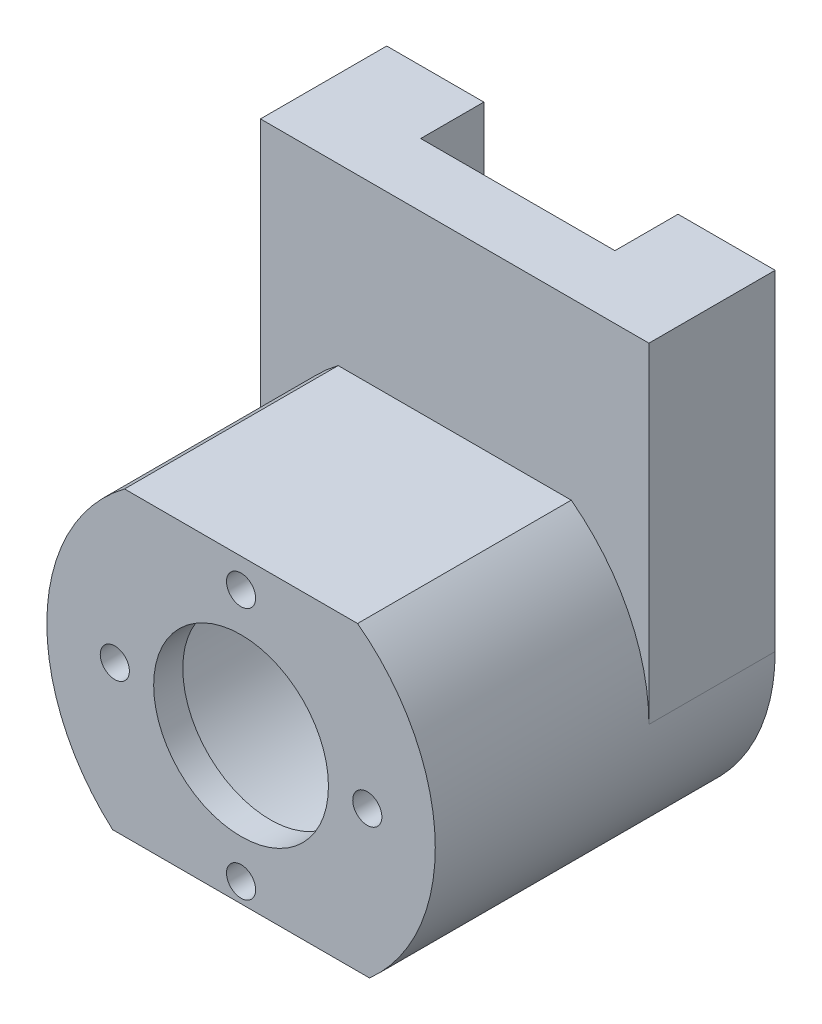
SolidWorks part; units mm, degrees
ref_plane "Plan de face" through (0, 0, 0) normal (0, 0, 1) x (1, 0, 0)
ref_plane "Plan de dessus" through (0, 0, 0) normal (0, 1, 0) x (1, 0, 0)
ref_plane "Plan de droite" through (0, 0, 0) normal (1, 0, 0) x (0, 0, -1)
sketch "Esquisse1" plane through (0, 0, 0) normal (0, 0, 1) x (1, 0, 0)
  line L1 (20, -20) -> (20, -75)
  line L3 (0, 0) -> (0, 23.2042) construction
  line L4 (-20, -20) -> (-20, -75)
  arc A0 (-20, -75) -> (20, -75) centre (0, -75) ccw
  arc A1 (20, -20) -> (-20, -20) centre (0, -20) ccw
  circle A2 centre (0, -75) radius 15
  circle A3 centre (0, -20) radius 5
  circle A4 centre (-14, -20) radius 2
  circle A5 centre (-9.8995, -10.1005) radius 2
  circle A6 centre (0, -6) radius 2
  circle A7 centre (9.8995, -10.1005) radius 2
  circle A8 centre (14, -20) radius 2
  circle A9 centre (9.8995, -29.8995) radius 2
  circle A10 centre (0, -34) radius 2
  circle A11 centre (-9.8995, -29.8995) radius 2
  dimension "D1" = 30
extrude "Extrusion1" add sketch "Esquisse1" along normal blind 5
sketch "Esquisse2" plane through (0, 0, 5) normal (0, 0, 1) x (1, 0, 0)
  line L1 (12, -59) -> (-12, -59)
  arc A0 (-12, -59) -> (12, -59) centre (0, -75) ccw
  circle A1 centre (0, -75) radius 9
  circle A3 centre (0, -62) radius 1.5
  circle A4 centre (0, -88) radius 1.5
  circle A5 centre (-13, -75) radius 1.5
  circle A6 centre (13, -75) radius 1.5
extrude "Extrusion2" add sketch "Esquisse2" along normal blind 30
sketch "Esquisse3" plane through (0, 0, 5) normal (0, 0, -1) x (-1, 0, 0)
  circle A0 centre (0, -75) radius 15
extrude "Extrusion3" cut sketch "Esquisse3" against normal blind 27
sketch "Esquisse4" plane through (0, 0, 0) normal (1, 0, 0) x (0, 0, -1)
  line L0 (-35, -95) -> (-30, -95)
  line L1 (-35, -95) -> (0, -95) construction
  line L2 (-35, -95) -> (-35, -90)
  line L3 (-35, -59) -> (-35, -95) construction
  line L4 (-35, -90) -> (-30, -95)
extrude "Extrusion4" cut sketch "Esquisse4" against normal through all and the other way through all
sketch "Esquisse5" plane through (0, 0, 5) normal (0, 0, 1) x (1, 0, 0)
  line L0 (20, -41) -> (-20, -41)
  line L2 (-20, -20) -> (-20, -41)
  line L5 (20, -20) -> (20, -41)
  arc A0 (20, -20) -> (-20, -20) centre (0, -20) ccw
extrude "Extrusion5" cut sketch "Esquisse5" against normal blind 10
sketch "Esquisse6" plane through (0, -41, 0) normal (0, 1, 0) x (1, 0, 0)
  line L0 (-20, -5) -> (-20, -13)
  line L1 (-20, -13) -> (20, -13)
  line L2 (20, -5) -> (20, -13)
  line L3 (-20, -5) -> (20, -5)
extrude "Extrusion6" add sketch "Esquisse6" against normal up to next
sketch "Esquisse7" plane through (0, -41, 0) normal (0, 1, 0) x (1, 0, 0)
  line L0 (10, 0) -> (-10, 0)
  line L1 (-20, 0) -> (20, 0) construction
  line L2 (10, 0) -> (10, -6.5)
  line L3 (10, -6.5) -> (-10, -6.5)
  line L4 (-10, -6.5) -> (-10, 0)
extrude "Extrusion7" cut sketch "Esquisse7" against normal up to next
